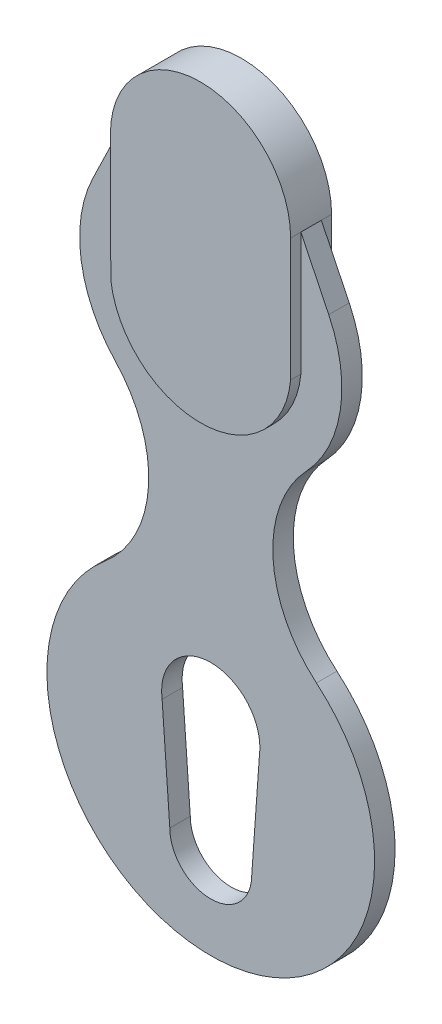
SolidWorks part; units mm, degrees
ref_plane "Front Plane" through (0, 0, 0) normal (0, 0, 1) x (1, 0, 0)
ref_plane "Top Plane" through (0, 0, 0) normal (0, 1, 0) x (1, 0, 0)
ref_plane "Right Plane" through (0, 0, 0) normal (1, 0, 0) x (0, 0, -1)
sketch "Sketch1" plane through (0, 0, 0) normal (0, 0, 1) x (1, 0, 0)
  line L0 (0, -1004) -> (0, -28) construction
  line L1 (1000, 0) -> (11.2857, 0) construction
  line L2 (-12, 10) -> (-10, -18)
  line L3 (12, 10) -> (10, -18)
  line L4 (-11.2857, 0) -> (-50000, 0) construction
  line L5 (0, 0) -> (0, 22) construction
  line L6 (0, 0) -> (-6.6332, 0) construction
  line L7 (0, -8) -> (0, -2) construction
  line L9 (22, 124) -> (22, 94)
  line L10 (-22, 124) -> (-21.9028, 93.1245)
  line L11 (10, 124) -> (10, 110)
  line L12 (-22, 124) -> (-28.8044, 109.9394)
  line L13 (12, 107.1716) -> (12, 96)
  line L14 (-10, 124) -> (-10, 110)
  line L15 (22, 124) -> (28.8044, 109.9394)
  line L16 (-12, 107.1716) -> (-12, 96)
  arc A0 (-25.7951, 30.5714) -> (25.7951, 30.5714) centre (0, 0) ccw
  arc A1 (11.8782, 8.2944) -> (-11.8782, 8.2944) centre (0, 10) ccw
  arc A2 (-10, -18) -> (10, -18) centre (0, -18) ccw
  arc A3 (22, 124) -> (-22, 124) centre (0, 124) ccw
  arc A4 (-21.9028, 93.1245) -> (22, 94) centre (0, 96) ccw
  arc A5 (10, 124) -> (-10, 124) centre (0, 124) ccw
  arc A6 (-12, 96) -> (6.2126, 85.7333) centre (0, 96) ccw
  arc A7 (-10, 110) -> (-12, 107.1716) centre (-9, 107.1716) ccw
  arc A8 (10, 110) -> (12, 107.1716) centre (9, 107.1716) cw
  arc A9 (-28.8044, 109.9394) -> (-23.2988, 74.0645) centre (0, 96) ccw
  arc A10 (23.2988, 74.0645) -> (25.7951, 30.5714) centre (45.1414, 53.5) ccw
  arc A11 (-23.2988, 74.0645) -> (-25.7951, 30.5714) centre (-45.1414, 53.5) cw
  arc A12 (23.2988, 74.0645) -> (28.8044, 109.9394) centre (0, 96) ccw
  point P23 (0, 110)
  dimension "D1" = 80
  dimension "D2" = 24
  dimension "D3" = 20
  dimension "D7" = 22
  dimension "D10" = 1
  dimension "D11" = 14
  dimension "D12" = 3
  dimension "D13" = 64
  dimension "D14" = 30
  dimension "D15" = 20
  dimension "D16" = 12
  dimension "D17" = 3
  dimension "D18" = 10
  dimension "D20" = 22
  dimension "D22" = 12
  dimension "D23" = 22.0907
  dimension "D4" = 28
  dimension "D5" = 10
  dimension "D6" = 10
  dimension "D8" = 28
  dimension "D9" = 128
  dimension "D19" = 30
extrude "Boss-Extrude2" add sketch "Sketch1" along normal mid plane 10 contours L10 A4 L9 A3 L11 A8 L13 A6 L16 A7 L14 A5 region at (0.0116, 109.9408, 0)
extrude "Boss-Extrude4" add sketch "Sketch1<7>" along normal mid plane 5 contours A10 A12 L15 L9 A4 L10 L12 A9 A11 A0 A2 L2 A1 L3 region at (-0.0052, 24.8952, 0)
sketch "Sketch1<7>" plane through (0, 0, 0) normal (0, 0, 1) x (1, 0, 0) same geometry as "Sketch1"
